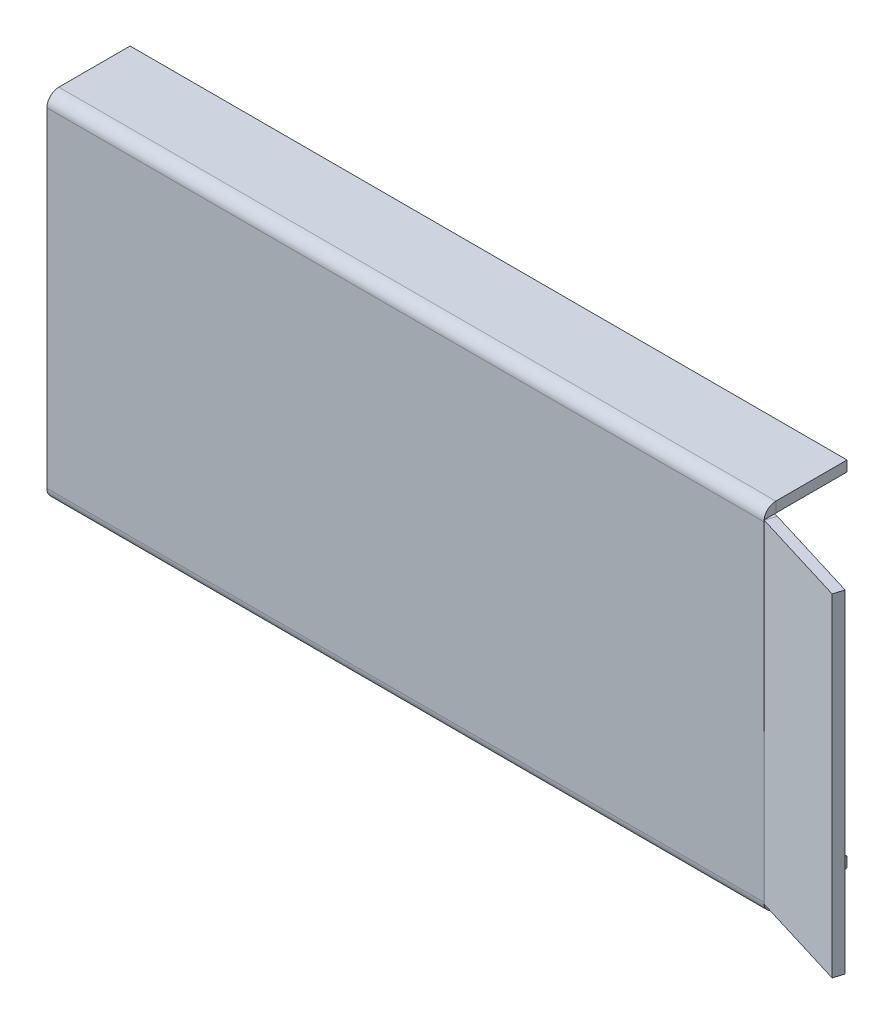
SolidWorks part; units mm, degrees
note: The reader was unsure of these and kept them because the rebuilt part matched: flange length of "Edge-Flange1", "Edge-Flange2".
ref_plane "Front Plane" through (0, 0, 0) normal (0, 0, 1) x (1, 0, 0)
ref_plane "Top Plane" through (0, 0, 0) normal (0, 1, 0) x (1, 0, 0)
ref_plane "Right Plane" through (0, 0, 0) normal (1, 0, 0) x (0, 0, -1)
sketch "Sketch1" plane through (0, 0, 0) normal (0, 0, 1) x (1, 0, 0)
  line L1 (0, 0) -> (345, 0)
  line L2 (0, 0) -> (0, -160)
  line L3 (0, -160) -> (345, -160)
  line L4 (345, 0) -> (345, -160)
  dimension "D1" = 160
  dimension "D2" = 345
base flange "Base-Flange1" sketch "Sketch1" thickness 5 reverse thickness direction no parameters "D1"=0.7366
edge flange "Edge-Flange1" sketch "Sketch9" flange angle 163 flange length 50 flange position material outside bend radius 0.7366 thickness 5 relief rectangular parameters "D6"=10
sketch "Sketch9" plane through (345, 0, 0) normal (0.2924, 0, -0.9563) x (0, 1, 0)
  line L0 (-160, 0) -> (0, 0) construction
  line L1 (-160, 0) -> (0, 0)
  line L2 (-160, 0) -> (-160, 49.2527)
  line L3 (-160, 49.2527) -> (0, 49.2527)
  line L4 (0, 49.2527) -> (0, 0)
bend "EdgeBend1" bend radius 0.7366 bend angle 17 parameters "D5"=1
edge flange "Edge-Flange2" sketch "Sketch14" flange profiles "Sketch14", "Sketch15" flange angle 90 flange length 40 flange position material outside bend radius 0.7366 thickness 5 relief none parameters "D6"=10, "D8"=1
sketch "Sketch14" plane through (0, -160, -5) normal (0, -1, 0) x (-1, 0, 0)
  line L0 (0, 0) -> (-344.8899, 0) construction
  line L1 (0, 0) -> (-344.8899, 0)
  line L2 (-344.8899, 0) -> (-344.8899, 35)
  line L3 (-344.8899, 35) -> (0, 35)
  line L4 (0, 35) -> (0, 0)
sketch "Sketch15" plane through (0, 0, -5) normal (0, 1, 0) x (1, 0, 0)
  line L0 (344.8899, 0) -> (0, 0) construction
  line L1 (344.8899, 0) -> (0, 0)
  line L2 (0, 0) -> (0, 35)
  line L3 (0, 35) -> (344.8899, 35)
  line L4 (344.8899, 35) -> (344.8899, 0)
bend "EdgeBend2" bend radius 0.7366 bend angle 90 parameters "D5"=2
bend "EdgeBend3" bend radius 0.7366 bend angle 90 parameters "D5"=3
sketch "Bend-Lines1" [suppressed] plane through (0, 0, 0) normal (0, 1, 0) x (1, 0, 0)
sketch "Bounding-Box1" [suppressed] plane through (0, 0, 0) normal (0, 1, 0) x (1, 0, 0)
sheet metal parameters "Sheet-Metal4" thickness 5 parameters "D1"=0.7366
flat pattern "Flat-Pattern4" [suppressed]
sketch "Bend-Lines2" plane through (0, 0, 0) normal (0, 1, 0) x (1, 0, 0)
sketch3d "Bounding-Box2" [suppressed]
  line L0 (0, -160, 0) -> (-345, -160, 0) construction
  line L1 (0, 0, 0) -> (-345, 0, 0) construction
  line L2 (0, -160, 0) -> (0, 0, 0) construction
  line L3 (-345, -160, 0) -> (-345, 0, 0) construction
sheet metal parameters "Sheet-Metal5" thickness 5 parameters "D1"=0.7366
flat pattern "Flat-Pattern4"
sketch "Bend-Lines2" plane through (0, 0, 0) normal (0, 0, 1) x (1, 0, 0)
  line L0 (344.9992, -160) -> (344.9992, 0) construction
  line L1 (344.9992, -160) -> (344.9992, 0) construction
sketch3d "Bounding-Box2" [suppressed]
  line L0 (0, -160, 0) -> (389.2511, -160, 0) construction
  line L1 (0, 0, 0) -> (389.2511, 0, 0) construction
  line L2 (0, -160, 0) -> (0, 0, 0) construction
  line L3 (389.2511, -160, 0) -> (389.2511, 0, 0) construction
bend of the flat pattern "Flatten-<EdgeBend1>1"
sheet metal parameters "Sheet-Metal6" thickness 5 parameters "D1"=0.7366
flat pattern "Flat-Pattern4"
sketch "Bend-Lines2" plane through (0, 0, 0) normal (0, 0, 1) x (1, 0, 0)
  line L0 (344.9992, -160) -> (344.9992, 0) construction
  line L1 (344.9992, -160) -> (344.9992, 0) construction
  line L2 (344.8899, -0.1581) -> (0, -0.1581) construction
  line L3 (0, -159.8419) -> (344.8899, -159.8419) construction
  line L4 (344.8899, -0.1581) -> (0, -0.1581) construction
  line L5 (0, -159.8419) -> (344.8899, -159.8419) construction
sketch3d "Bounding-Box2" [suppressed]
  line L0 (0, -194.6838, 0) -> (394.2511, -194.6838, 0) construction
  line L1 (0, 34.6838, 0) -> (394.2511, 34.6838, 0) construction
  line L2 (0, -194.6838, 0) -> (0, 34.6838, 0) construction
  line L3 (394.2511, -194.6838, 0) -> (394.2511, 34.6838, 0) construction
bend of the flat pattern "Flatten-<EdgeBend1>1"
bend of the flat pattern "Flatten-<EdgeBend2>1"
bend of the flat pattern "Flatten-<EdgeBend3>1"
